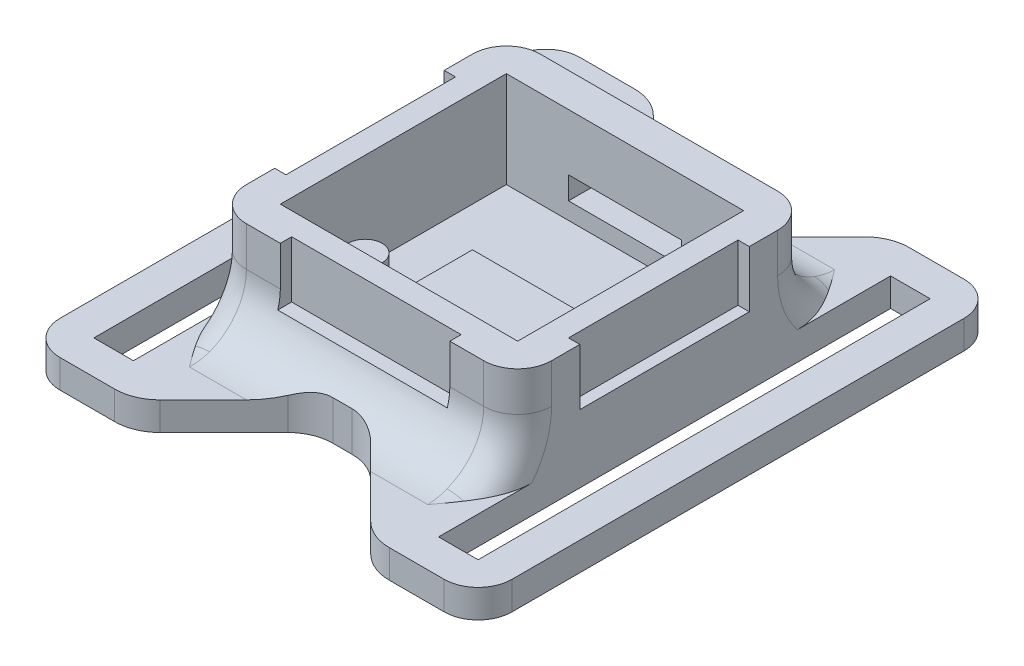
SolidWorks part; units mm, degrees
ref_plane "Front" through (0, 0, 0) normal (0, 0, 1) x (1, 0, 0)
ref_plane "Top" through (0, 0, 0) normal (0, 1, 0) x (1, 0, 0)
ref_plane "Right" through (0, 0, 0) normal (1, 0, 0) x (0, 0, -1)
sketch "Sketch1" plane through (0, 0, 0) normal (0, 1, 0) x (1, 0, 0)
  line L0 (0, 0) -> (0, -67169.9944) construction
  line L5 (0, 0) -> (-67169.9944, 0) construction
  line L6 (-17, 0) -> (-17, -20)
  line L7 (-17, -20) -> (-13.5, -20)
  line L8 (-13.5, -20) -> (-13.5, 0)
  line L9 (-20, 0) -> (-20, -20)
  line L10 (-17, -23) -> (-13.5, -23)
  line L11 (-20, 0) -> (-17, 0)
  line L12 (0, 0) -> (0, -15)
  line L15 (-13.5, 0) -> (0, 0)
  line L16 (-13.5, -23) -> (-10.5, -23)
  line L19 (-10.5, -23) -> (-2.5, -15)
  line L20 (-2.5, -15) -> (0, -15)
  line L21 (-10.5, -12) -> (-13.5, -12) construction
  line L22 (-10.5, 3) -> (10.5, 3) construction
  line L23 (-10.5, 3) -> (-10.5, -12) construction
  line L24 (-10.5, -12) -> (10.5, -12) construction
  line L25 (10.5, 3) -> (10.5, -12) construction
  line L26 (-10.5, 3) -> (10.5, -12) construction
  line L27 (-10.5, -12) -> (10.5, 3) construction
  arc A0 (-20, -20) -> (-17, -23) centre (-17, -20) ccw
  point P24 (0, -4.5)
  dimension "D5" = 3
  dimension "D1" = 3.5
  dimension "D2" = 20
  dimension "D3" = 3
  dimension "D4" = 3
  dimension "D6" = 15
  dimension "D7" = 3
  dimension "D8" = 45
  dimension "D9" = 3
  dimension "D10" = 21
  dimension "D11" = 15
  dimension "D12" = 3
extrude "Boss-Extrude1" add sketch "Sketch1" along normal blind 2.5
sketch "Sketch2" plane through (0, 2.5, 0) normal (0, 1, 0) x (1, 0, 0)
  line L0 (0, -13) -> (-13.5, -13)
  line L1 (0, -15) -> (0, 0) construction
  line L2 (-13.5, 0) -> (-13.5, -20) construction
  line L3 (-13.5, -13) -> (-13.5, 0)
  line L4 (-13.5, 0) -> (-10.5, 0)
  line L5 (0, 0) -> (-13.5, 0) construction
  line L6 (-10.5, 0) -> (-10.5, -10)
  line L7 (-10.5, -10) -> (0, -10)
  line L8 (0, -10) -> (0, -13)
  point P15 (0, 0)
  point P16 (0, 0)
  point P17 (0, 0)
  dimension "D1" = 3
  dimension "D2" = 10
extrude "Boss-Extrude2" add sketch "Sketch2" along normal blind 8.5
fillet "Fillet4" radius 5 1 edges at (-6.75, 2.5, 13)
fillet "Fillet3" radius 4 2 edges at (-2.5, 1.75, 15) (-10.5, 1.25, 23)
fillet "Fillet5" radius 3 3 edges at (-13.5, 2.5, 19) (-13.5, 3.9645, 14.4645) (-13.5, 9.25, 13)
sketch "Sketch12" plane through (0, 0, 20) normal (0, 0, -1) x (-1, 0, 0)
  line L0 (13.5, 0) -> (13.5, 2.5)
  line L1 (13.5, 0) -> (17, 0) construction
  line L2 (10.542, 2.5) -> (17, 2.5) construction
  line L3 (13.5, 2.5) -> (10.542, 2.5)
  line L4 (10.542, 2.5) -> (10.542, 0)
  line L5 (0, 0) -> (13.5, 0) construction
  line L6 (10.542, 0) -> (13.5, 0)
  point P6 (0, 0)
  point P12 (0, 0)
extrude "Boss-Extrude5" add sketch "Sketch12" along normal up to vertex (20 mm away) up to point (-13.5, 0, 0)
mirror "Mirror1" about plane through (0, 0, 0) normal (1, 0, 0) of bodies 126 115
mirror "Mirror2" about plane through (0, 0, 0) normal (0, 0, 1) of bodies 116
sketch "Sketch3" plane through (0, 2.5, 0) normal (0, 1, 0) x (1, 0, 0)
  line L0 (10.5, -10) -> (-10.5, -10) construction
  line L1 (-13.75, -10) -> (13.75, -10) construction
  line L2 (-13.75, -10) -> (-13.75, 8) construction
  line L3 (-13.75, 8) -> (13.75, 8) construction
  line L4 (13.75, -10) -> (13.75, 8) construction
  line L5 (-13.75, -10) -> (13.75, 8) construction
  line L6 (-13.75, 8) -> (13.75, -10) construction
  line L7 (0, 8) -> (0, 10) construction
  line L8 (10.5, 10) -> (-10.5, 10) construction
  line L9 (-7.5, -5.5) -> (-7.5, -10) construction
  line L10 (-7.5, -5.5) -> (7.5, -5.5) construction
  line L11 (-13.75, -10) -> (-7.5, -10) construction
  line L12 (7.5, -5.5) -> (7.5, -10) construction
  line L13 (7.5, -10) -> (13.75, -10) construction
  line L15 (-5, -3.5) -> (5, -3.5)
  line L16 (-5, -3.5) -> (-5, 1.5)
  line L17 (-5, 1.5) -> (5, 1.5)
  line L18 (5, -3.5) -> (5, 1.5)
  line L19 (-5, -3.5) -> (5, 1.5) construction
  line L20 (-5, 1.5) -> (5, -3.5) construction
  circle A0 centre (-7.5, -5.5) radius 2
  circle A1 centre (7.5, -5.5) radius 2
  circle A2 centre (-7.5, -5.5) radius 1.5
  circle A3 centre (7.5, -5.5) radius 1.5
  point P0 (0, -1)
  point P20 (0, -1)
  dimension "D5" = 4
  dimension "D7" = 3
  dimension "D1" = 27.5
  dimension "D2" = 18
  dimension "D3" = 2
  dimension "D4" = 4.5
  dimension "D6" = 15
  dimension "D8" = 5
  dimension "D9" = 10
  dimension "D10" = 2
extrude "Boss-Extrude3" add sketch "Sketch3" along normal blind 2 contours L15 L18 L17 L16 | A0 | A1 region at (0, 2.5, 1)
extrude "Boss-Extrude4" add sketch "Sketch3<4>" along normal blind 4 contours A2 | A3 region at (-7.5, 2.5, 5.5)
sketch "Sketch3<4>" plane through (0, 2.5, 0) normal (0, 1, 0) x (1, 0, 0) same geometry as "Sketch3"
sketch "Sketch11" plane through (0, 11, 0) normal (0, 1, 0) x (1, 0, 0)
  line L0 (-10.5, 0) -> (10.5, 0) construction
  line L1 (-10.5, -10) -> (-10.5, 10) construction
  line L2 (10.5, -10) -> (10.5, 10) construction
  line L3 (0, 0) -> (0, -10) construction
  line L4 (10.5, -10) -> (-10.5, -10) construction
  line L5 (-12.5, 0) -> (-10.5, 0) construction
  line L6 (-15, -7.5) -> (-12.5, -7.5)
  line L7 (-15, -7.5) -> (-15, 7.5)
  line L8 (-15, 7.5) -> (-12.5, 7.5)
  line L9 (-12.5, -7.5) -> (-12.5, 7.5)
  line L10 (-15, -7.5) -> (-12.5, 7.5) construction
  line L11 (-15, 7.5) -> (-12.5, -7.5) construction
  line L12 (15, 7.5) -> (12.5, 7.5)
  line L13 (12.5, -7.5) -> (12.5, 7.5)
  line L14 (15, -7.5) -> (12.5, -7.5)
  line L15 (15, -7.5) -> (15, 7.5)
  line L16 (0, -12) -> (0, -10) construction
  line L17 (-7.5, -14.5) -> (7.5, -14.5)
  line L18 (-7.5, -14.5) -> (-7.5, -12)
  line L19 (-7.5, -12) -> (7.5, -12)
  line L20 (7.5, -14.5) -> (7.5, -12)
  line L21 (-7.5, -14.5) -> (7.5, -12) construction
  line L22 (-7.5, -12) -> (7.5, -14.5) construction
  point P11 (-13.75, 0)
  point P22 (0, -13.25)
  dimension "D1" = 2
  dimension "D2" = 15
  dimension "D3" = 2.5
extrude "Cut-Extrude3" cut sketch "Sketch11" against normal blind 5
sketch "Sketch8" plane through (0, 0, -10) normal (0, 0, -1) x (-1, 0, 0)
  line L0 (0, 0) -> (0, 5) construction
  line L1 (-5, 4) -> (5, 4)
  line L2 (-5, 4) -> (-5, 6)
  line L3 (-5, 6) -> (5, 6)
  line L4 (5, 4) -> (5, 6)
  line L5 (-5, 4) -> (5, 6) construction
  line L6 (-5, 6) -> (5, 4) construction
  line L7 (-10.5, 2.5) -> (10.5, 2.5) construction
  point P0 (0, 5)
  dimension "D1" = 10
  dimension "D2" = 2
  dimension "D3" = 1.5
extrude "Cut-Extrude4" cut sketch "Sketch8" along normal blind 10
